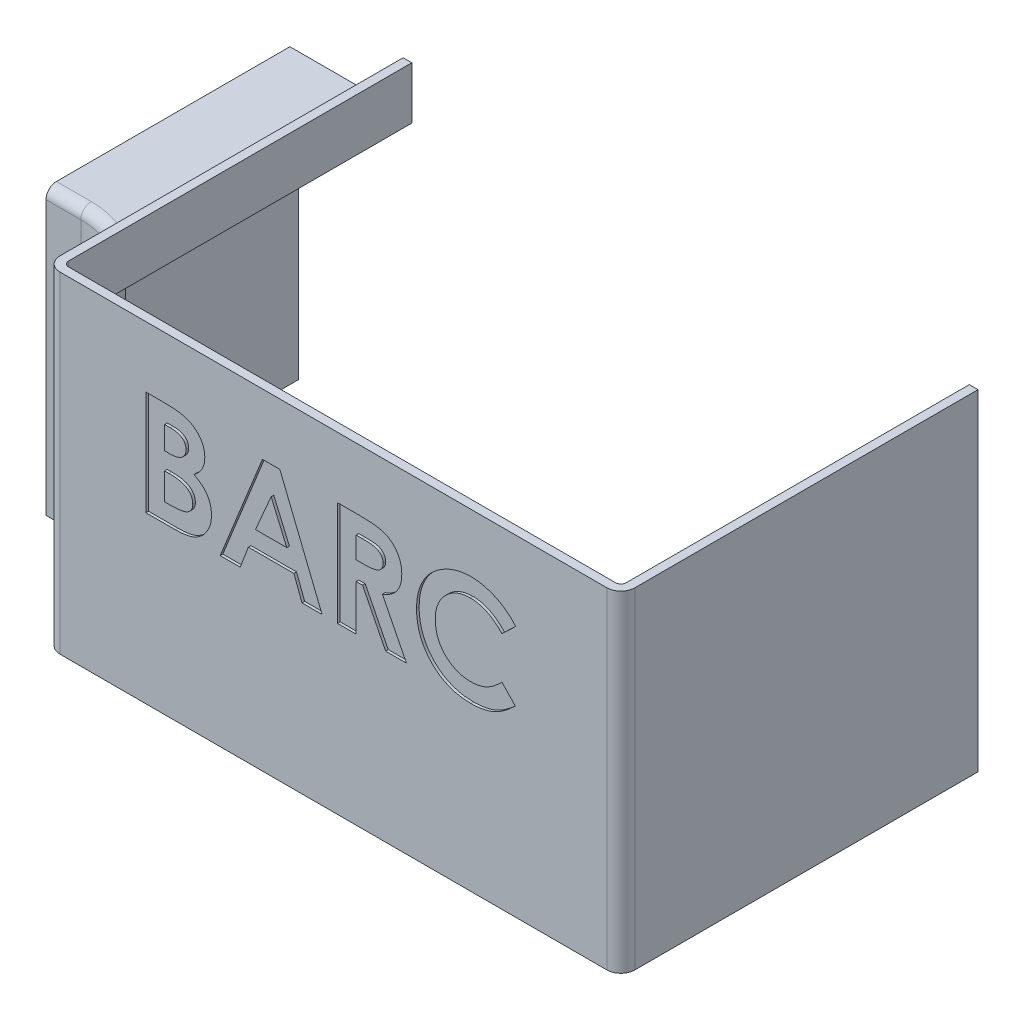
SolidWorks part; units mm, degrees
ref_plane "Front Plane" through (0, 0, 0) normal (0, 0, 1) x (1, 0, 0)
ref_plane "Top Plane" through (0, 0, 0) normal (0, 1, 0) x (1, 0, 0)
ref_plane "Right Plane" through (0, 0, 0) normal (1, 0, 0) x (0, 0, -1)
sketch "Sketch1" plane through (0, 0, 0) normal (0, 1, 0) x (1, 0, 0)
  line L0 (0, 3) -> (0, 15)
  line L1 (3, 0) -> (317, 0)
  line L2 (320, 3) -> (320, 200)
  line L3 (-50, 65) -> (-65, 65)
  line L4 (-65, 65) -> (-65, 200)
  arc A0 (0, 15) -> (-50, 65) centre (-50, 15) ccw
  arc A1 (320, 3) -> (317, 0) centre (317, 3) cw
  arc A2 (3, 0) -> (0, 3) centre (3, 3) cw
  point P9 (0, 65)
  point P12 (320, 0)
  point P15 (0, 0)
  dimension "D5" = 50
  dimension "D6" = 3
  dimension "D1" = 200
  dimension "D2" = 320
  dimension "D3" = 65
  dimension "D4" = 65
extrude "Extrude-Thin1" add sketch "Sketch1" along normal blind 190 thin thin type one direction reverse wall 5
sketch "Sketch2" plane through (0, 190, 0) normal (0, 1, 0) x (1, 0, 0)
  line L0 (-70, 200) -> (0, 200)
  line L1 (0, 15) -> (0, 200)
  line L3 (-70, 60) -> (-70, 200) construction
  line L4 (-50, 60) -> (-70, 60) construction
  line L5 (-70, 60) -> (-70, 200)
  line L6 (-50, 60) -> (-70, 60)
  line L7 (-5, 15) -> (0, 15)
  arc A0 (-5, 15) -> (-50, 60) centre (-50, 15) ccw construction
  arc A1 (-5, 15) -> (-50, 60) centre (-50, 15) ccw
extrude "Boss-Extrude1" add sketch "Sketch2" against normal blind 30
sketch "Sketch3" plane through (0, 0, 5) normal (0, 0, 1) x (1, 0, 0)
  line L0 (3, 95) -> (317, 95) construction
  line L1 (3, 190) -> (3, 0) construction
  line L2 (317, 190) -> (317, 0) construction
  text T0 "<b>BARC</b>" font "Century Gothic" height 60
extrude "Cut-Extrude1" cut sketch "Sketch3" against normal blind 1.5
ref_plane "Plane1" through (0, 150, 0) normal (0, 1, 0) x (-1, 0, 0)
sketch "Sketch5" plane through (0, 150, 0) normal (0, 1, 0) x (-1, 0, 0)
  line L0 (-320, -20) -> (-300, 0)
  line L1 (-317, 0) -> (-3, 0) construction
  line L2 (-320, -200) -> (-320, -3) construction
  dimension "D1" = 20
  dimension "D2" = 20
rib "Rib1" sketch "Sketch5" sketch "Sketch5" thickness 2.5 extrusion direction parallel to sketch draft on no parameters "D1"=2.5
fillet "Fillet1" radius 10 2 edges at (300, 150, 0) (320, 150, -20)
pattern_linear "LPattern1" count 3 spacing 50 along (0, -1, 0) of "Fillet1", "Rib1"
sketch "Sketch7" plane through (0, 190, 0) normal (0, 1, 0) x (1, 0, 0)
  line L0 (317, 0) -> (3, 0) construction
  point P0 (160, 0)
ref_plane "Plane2" through (160, 0, 0) normal (-1, 0, 0) x (0, 0, 1)
mirror "Mirror1" [suppressed] about plane through (160, 0, 0) normal (-1, 0, 0)
sketch "Sketch8" plane through (0, 0, -200) normal (0, 0, -1) x (-1, 0, 0)
  line L0 (5, 190) -> (5, 163)
  line L1 (5, 163) -> (70, 163)
  line L2 (70, 190) -> (70, 0) construction
  line L3 (5, 190) -> (70, 190)
  line L4 (70, 190) -> (70, 163)
  line L5 (0, 160) -> (50, 160) construction
  dimension "D1" = 3
extrude "Cut-Extrude2" cut sketch "Sketch8" against normal through all
fillet "Fillet2" radius 10 1 edges at (-5, 163, -107.5)
fillet "Fillet3" radius 6 3 edges at (-60, 163, -60) (-30.6066, 163, -55.6066) (-10.3164, 164.1646, -36.2182)
fillet "Fillet5" radius 10 1 edges at (-65, 80, -65)
